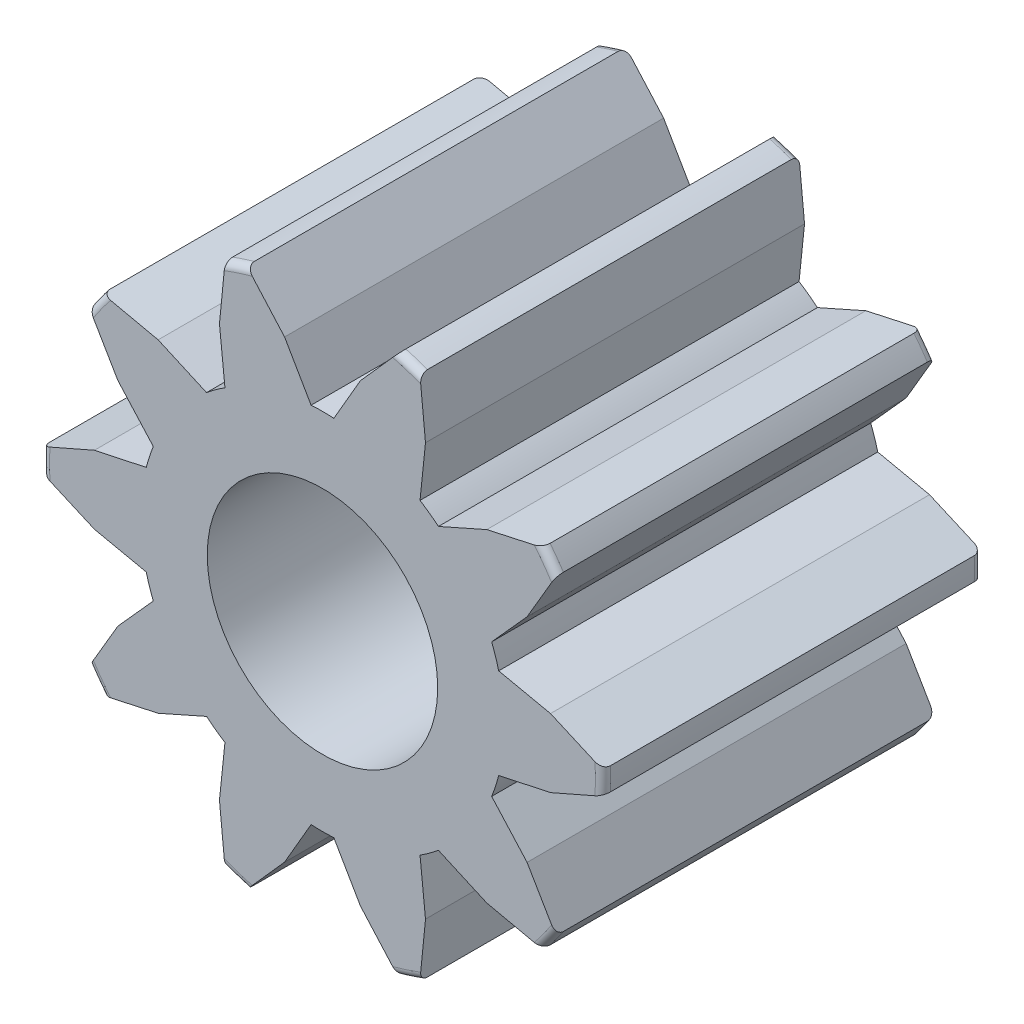
SolidWorks part; units mm, degrees
note: The reader was unsure of these and kept them because the rebuilt part matched: shared geometry of "Croquis2<3>".
material "Aleación 1060"
ref_plane "Alzado" through (0, 0, 0) normal (0, 0, 1) x (1, 0, 0)
ref_plane "Planta" through (0, 0, 0) normal (0, 1, 0) x (1, 0, 0)
ref_plane "Vista lateral" through (0, 0, 0) normal (1, 0, 0) x (0, 0, -1)
sketch "Croquis1" plane through (0, 0, 0) normal (0, 0, 1) x (1, 0, 0)
  circle A0 centre (0, 0) radius 1.85
  dimension "D1" = 3.7
extrude "Saliente-Extruir1" add sketch "Croquis1" along normal blind 2.5
sketch "Croquis2" plane through (0, 0, 2.5) normal (0, 0, 1) x (1, 0, 0)
  line L0 (0, 0) -> (0, 1.9555) construction
  line L1 (0.5, 2.25) -> (-0.5, 2.25)
  line L2 (-0.5, 2.25) -> (-0.5, 1.7812)
  line L3 (-0.5, 1.7812) -> (-0.25, 1.5)
  line L4 (-0.25, 1.5) -> (-0.075, 1.1977)
  line L5 (0.5, 1.7812) -> (0.25, 1.5)
  line L6 (0.5, 2.25) -> (0.5, 1.7812)
  line L7 (0.25, 1.5) -> (0.075, 1.1977)
  circle A0 centre (0, 0) radius 1.2
  circle A1 centre (0, 0) radius 1.85 construction
  circle A2 centre (0, 0) radius 0.76
  point P15 (0, 2.25)
  dimension "D1" = 0.65
  dimension "D2" = 1.52
  dimension "D3" = 0.5
  dimension "D4" = 0.075
  dimension "D5" = 0.25
  dimension "D6" = 1.5
  dimension "D7" = 2.25
extrude "Cortar-Extruir1" cut sketch "Croquis2" against normal blind 2.85
fillet "Redondeo1" radius 0.05 2 edges at (0, -1.85, 0) (0, -1.85, 2.5)
pattern_circular "MatrizC1" count 10 over 360 about axis through (0, 0, 0) along (0, 0, 1) of "Cortar-Extruir1"
extrude "Cortar-Extruir2" cut sketch "Croquis2<3>" against normal blind 2.85
sketch "Croquis2<3>" plane through (0, 0, 2.5) normal (0, 0, 1) x (1, 0, 0) same geometry as "Croquis2"
